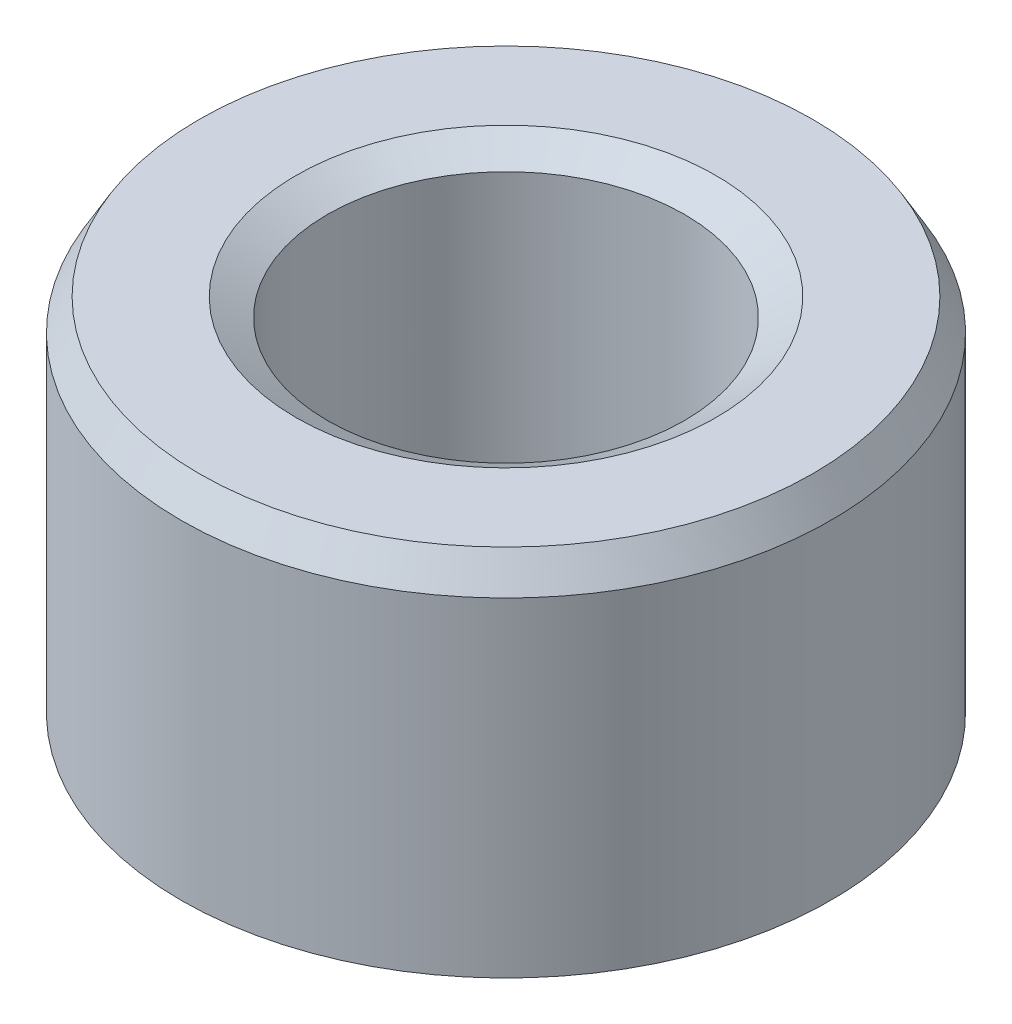
SolidWorks part; units mm, degrees
ref_plane "Front Plane" through (0, 0, 0) normal (0, 0, 1) x (1, 0, 0)
ref_plane "Top Plane" through (0, 0, 0) normal (0, 1, 0) x (1, 0, 0)
ref_plane "Right Plane" through (0, 0, 0) normal (1, 0, 0) x (0, 0, -1)
sketch "Sketch1" plane through (0, 0, 0) normal (0, 1, 0) x (1, 0, 0)
  circle A0 centre (0, 0) radius 32.5
  dimension "SLEEVE_OD" = 65
extrude "Boss-Extrude1" add sketch "Sketch1" along normal blind 37.8568
sketch "Sketch2" plane through (0, 0, 0) normal (0, 1, 0) x (1, 0, 0)
  circle A0 centre (0, 0) radius 17.8562
  dimension "BORE_D" = 35.7124
extrude "Cut-Extrude1" cut sketch "Sketch2" along normal through all
chamfer "Chamfer1" distance 3.132 angle 30.086 4 edges at (0, 37.8568, 17.8562) (0, 0, 17.8562) (0, 0, 32.5) (0, 37.8568, 32.5) first distance on face at (0, 37.8568, 17.8562) first distance on face at (0, 0, 17.8562) first distance on face at (0, 37.8568, 32.5)
